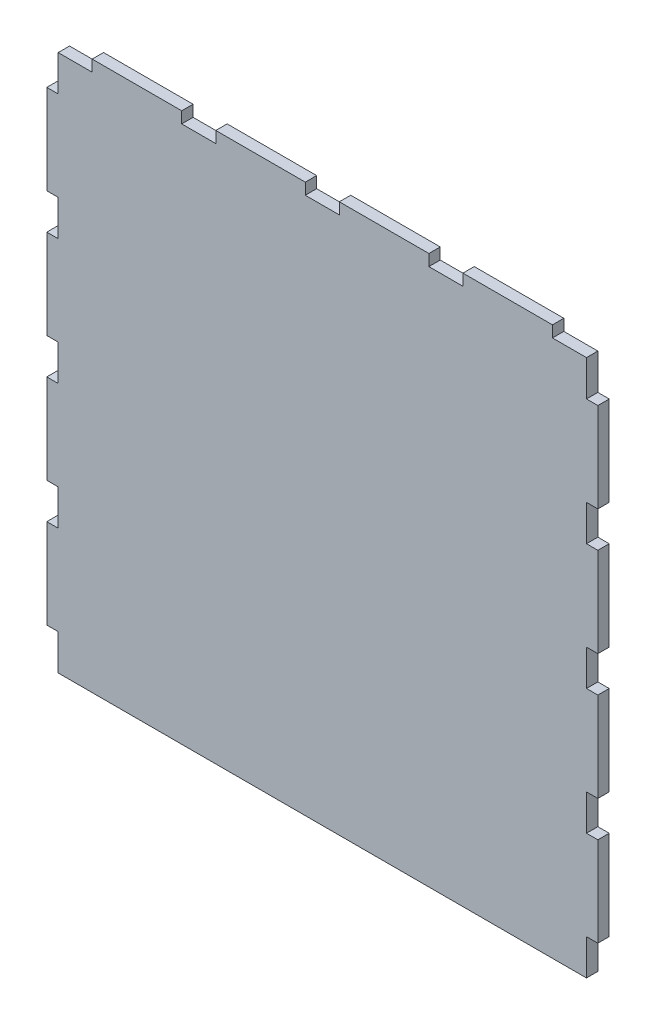
SolidWorks part; units mm, degrees
material "Beech"
ref_plane "Front Plane" through (0, 0, 0) normal (0, 0, 1) x (1, 0, 0)
ref_plane "Top Plane" through (0, 0, 0) normal (0, 1, 0) x (1, 0, 0)
ref_plane "Right Plane" through (0, 0, 0) normal (1, 0, 0) x (0, 0, -1)
sketch "Sketch2" plane through (0, 0, 0) normal (0, 0, 1) x (1, 0, 0)
  line L1 (0, 0) -> (19, 0)
  line L2 (0, 0) -> (0, -20)
  line L3 (0, -300) -> (295, -300)
  line L4 (295, 0) -> (295, -20)
  line L6 (19, 0) -> (19, 6.35)
  line L7 (19, 6.35) -> (69, 6.35)
  line L8 (69, 0) -> (69, 6.35)
  line L9 (88, 0) -> (88, 6.35)
  line L10 (88, 6.35) -> (138, 6.35)
  line L11 (138, 0) -> (138, 6.35)
  line L13 (157, 0) -> (157, 6.35)
  line L14 (157, 6.35) -> (207, 6.35)
  line L15 (207, 0) -> (207, 6.35)
  line L17 (226, 0) -> (226, 6.35)
  line L18 (226, 6.35) -> (276, 6.35)
  line L19 (276, 0) -> (276, 6.35)
  line L20 (69, 0) -> (88, 0)
  line L21 (138, 0) -> (157, 0)
  line L22 (207, 0) -> (226, 0)
  line L23 (276, 0) -> (295, 0)
  line L24 (0, -90) -> (-6.35, -90)
  line L25 (0, -20) -> (-6.35, -20)
  line L27 (0, -70) -> (-6.35, -70)
  line L28 (-6.35, -20) -> (-6.35, -70)
  line L30 (0, -140) -> (-6.35, -140)
  line L31 (-6.35, -90) -> (-6.35, -140)
  line L32 (0, -160) -> (-6.35, -160)
  line L34 (0, -210) -> (-6.35, -210)
  line L35 (-6.35, -160) -> (-6.35, -210)
  line L36 (0, -230) -> (-6.35, -230)
  line L38 (0, -280) -> (-6.35, -280)
  line L39 (-6.35, -230) -> (-6.35, -280)
  line L40 (295, -90) -> (301.35, -90)
  line L41 (295, -20) -> (301.35, -20)
  line L43 (295, -70) -> (301.35, -70)
  line L44 (301.35, -20) -> (301.35, -70)
  line L45 (295, -140) -> (301.35, -140)
  line L46 (301.35, -90) -> (301.35, -140)
  line L47 (295, -160) -> (301.35, -160)
  line L48 (295, -210) -> (301.35, -210)
  line L49 (301.35, -160) -> (301.35, -210)
  line L50 (295, -230) -> (301.35, -230)
  line L51 (295, -280) -> (301.35, -280)
  line L52 (301.35, -230) -> (301.35, -280)
  line L53 (0, -70) -> (0, -90)
  line L54 (0, -140) -> (0, -160)
  line L55 (0, -210) -> (0, -230)
  line L56 (0, -280) -> (0, -300)
  line L57 (295, -70) -> (295, -90)
  line L58 (295, -140) -> (295, -160)
  line L59 (295, -210) -> (295, -230)
  line L60 (295, -280) -> (295, -300)
  dimension "D1" = 295
  dimension "D2" = 300
  dimension "D3" = 6.35
  dimension "D4" = 50
  dimension "D5" = 19
  dimension "D7" = 19
  dimension "D8" = 6.35
  dimension "D9" = 50
  dimension "D10" = 20
  dimension "D12" = 20
  dimension "D13" = 6.35
  dimension "D14" = 20
  dimension "D15" = 50
  dimension "D17" = 20
  dimension "D6" = 4
  dimension "D11" = 4
  dimension "D16" = 4
extrude "Boss-Extrude1" add sketch "Sketch2" along normal blind 6.35
